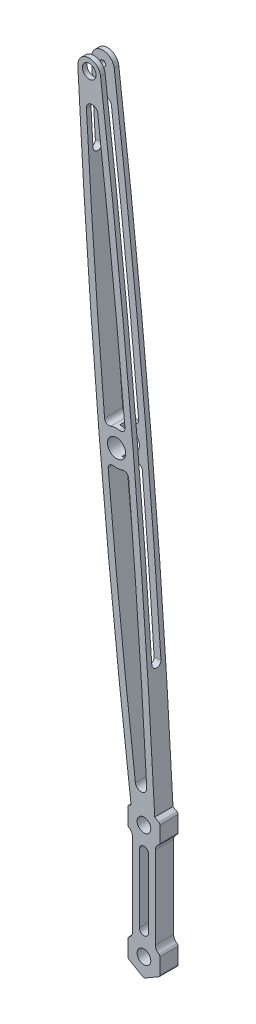
SolidWorks part; units mm, degrees
material "A2017"
ref_plane "正面" through (0, 0, 0) normal (0, 0, 1) x (1, 0, 0)
ref_plane "平面" through (0, 0, 0) normal (0, 1, 0) x (1, 0, 0)
ref_plane "右側面" through (0, 0, 0) normal (1, 0, 0) x (0, 0, -1)
sketch "ｽｹｯﾁ1" plane through (0, 0, 0) normal (0, 0, 1) x (1, 0, 0)
  line L0 (0, 0) -> (9.0749, 0) construction
  line L1 (0, 25) -> (0, 0) construction
  line L2 (0, -16.9171) -> (7, -20.9585)
  line L3 (7, 20.9585) -> (7, 29.0415)
  line L4 (7, 29.0415) -> (0, 33.0829)
  line L5 (0, 33.0829) -> (-7, 29.0415)
  line L6 (-7, 29.0415) -> (-7, 20.9585)
  line L7 (-7, 20.9585) -> (0, 16.9171)
  line L8 (0, 16.9171) -> (7, 20.9585)
  line L9 (-7, -20.9585) -> (0, -16.9171)
  line L10 (-7, -29.0415) -> (-7, -20.9585)
  line L11 (0, -33.0829) -> (-7, -29.0415)
  line L12 (7, -29.0415) -> (0, -33.0829)
  line L13 (7, -20.9585) -> (7, -29.0415)
  circle A0 centre (0, 25) radius 3
  circle A1 centre (0, -25) radius 3
  circle A2 centre (0, 25) radius 7 construction
  circle A3 centre (0, -25) radius 7 construction
  dimension "D1" = 6
  dimension "D2" = 50
  dimension "D3" = 14
extrude "ﾎﾞｽ - 押し出し1" add sketch "ｽｹｯﾁ1" along normal mid plane 8
sketch "ｽｹｯﾁ2" plane through (0, 0, 4) normal (0, 0, 1) x (1, 0, 0)
  line L0 (-7, 20.9585) -> (0, 16.9171) construction
  line L1 (5, -19.8038) -> (-5, -19.8038)
  line L2 (5, -19.8038) -> (5, 19.8038)
  line L3 (5, 19.8038) -> (-5, 19.8038)
  line L4 (-5, -19.8038) -> (-5, 19.8038)
  line L5 (5, -19.8038) -> (-5, 19.8038) construction
  line L6 (5, 19.8038) -> (-5, -19.8038) construction
  point P0 (0, 0)
  dimension "D1" = 10
extrude "ﾎﾞｽ - 押し出し2" add sketch "ｽｹｯﾁ2" against normal up to surface (8 mm away) up to face at (0, 25, -4)
fillet "ﾌｨﾚｯﾄ1" radius 3 4 edges at (5, -19.8038, 0) (-5, 19.8038, 0) (-5, -19.8038, 0) (5, 19.8038, 0)
fillet "ﾌｨﾚｯﾄ2" radius 1 10 edges at (-7, 20.9585, 0) (-7, 29.0415, 0) (0, 33.0829, 0) (7, 29.0415, 0) (7, 20.9585, 0) (7, -29.0415, 0) (0, -33.0829, 0) (-7, -29.0415, 0) (-7, -20.9585, 0) (7, -20.9585, 0)
sketch "ｽｹｯﾁ3" plane through (0, 0, -4) normal (0, 0, -1) x (-1, 0, 0)
  line L0 (0, -15) -> (0, 15) construction
  line L1 (-2, -15) -> (-2, 15)
  line L2 (2, -15) -> (2, 15)
  arc A0 (-2, -15) -> (2, -15) centre (0, -15) ccw
  arc A1 (2, 15) -> (-2, 15) centre (0, 15) ccw
  point P2 (0, 0)
  dimension "D1" = 4
  dimension "D2" = 30
extrude "ｶｯﾄ - 押し出し1" cut sketch "ｽｹｯﾁ3" against normal up to surface (8 mm away) up to face at (0, 0, 4)
sketch "ｽｹｯﾁ5" plane through (0, 0, 4) normal (0, 0, 1) x (1, 0, 0)
  circle A0 centre (0, -25) radius 3 construction
  circle A1 centre (0, 25) radius 3 construction
  circle A2 centre (0, -25) radius 3
  circle A3 centre (0, 25) radius 3
extrude "ﾎﾞｽ - 押し出し3" [suppressed] add sketch "ｽｹｯﾁ5" against normal blind 5
sketch "ｽｹｯﾁ8" plane through (0, 0, -4) normal (0, 0, -1) x (-1, 0, 0)
  circle A0 centre (0, -25) radius 3 construction
  circle A1 centre (0, 25) radius 3 construction
  circle A2 centre (0, -25) radius 3
  circle A3 centre (0, 25) radius 3
extrude "ﾎﾞｽ - 押し出し4" add sketch "ｽｹｯﾁ8" against normal blind 2.5
hole_wizard "M3 すきま穴1" positions "ｽｹｯﾁ6" profile "ｽｹｯﾁ7" hole size "M3" standard "JIS" end condition through all
sketch "ｽｹｯﾁ6" plane through (0, 0, 4) normal (0, 0, -1) x (-1, 0, 0)
  point P0 (0, 25)
  point P3 (0, -25)
sketch "ｽｹｯﾁ7" plane through (0, 25, 4) normal (1, 0, 0) x (0, -1, 0)
  line L0 (0, 0) -> (0, 8)
  line L1 (0, 8) -> (1.7, 8)
  line L2 (1.7, 8) -> (1.7, 0)
  line L5 (1.7, 0) -> (0, 0)
  line L11 (0, -6.35) -> (0, 107.95) construction
  dimension "通し穴の直径" = 3.4
  dimension "通し穴の深さ" = 8
sketch "ｽｹｯﾁ9" plane through (0, 0, 4) normal (0, 0, 1) x (1, 0, 0)
  line L0 (0, 25) -> (0, 298.9535) construction
  line L1 (0, 25) -> (-23.9678, 298.9535) construction
  line L2 (0, 25) -> (-23.9678, 298.9535) construction
  line L3 (-7.4715, 24.3463) -> (-31.4393, 298.2999) construction
  line L4 (7.4715, 25.6537) -> (-16.4964, 299.6072) construction
  line L15 (-7, 28.4641) -> (-7, 21.5359)
  line L16 (-5, 18.0718) -> (-5, -18.0718)
  line L17 (-7, -21.5359) -> (-7, -28.4641)
  line L18 (-6.5, -29.3301) -> (-0.5, -32.7942)
  line L19 (0.5, -32.7942) -> (6.5, -29.3301)
  line L20 (7, -28.4641) -> (7, -21.5359)
  line L21 (5, -18.0718) -> (5, 18.0718)
  line L22 (7, 21.5359) -> (7, 28.4641)
  line L23 (6.5, 29.3301) -> (0.5, 32.7942)
  line L24 (-0.5, 32.7942) -> (-6.5, 29.3301)
  line L25 (-7, 28.4641) -> (-7, 21.5359)
  line L26 (-5, 18.0718) -> (-5, -18.0718)
  line L27 (-7, -21.5359) -> (-7, -28.4641)
  line L28 (-6.5, -29.3301) -> (-0.5, -32.7942)
  line L29 (0.5, -32.7942) -> (6.5, -29.3301)
  line L30 (7, -28.4641) -> (7, -21.5359)
  line L31 (5, -18.0718) -> (5, 18.0718)
  line L32 (7, 21.5359) -> (7, 28.4641)
  line L33 (6.5, 29.3301) -> (0.5, 32.7942)
  line L34 (-0.5, 32.7942) -> (-6.5, 29.3301)
  arc A0 (-7.4715, 24.3463) -> (7.4715, 25.6537) centre (0, 25) ccw construction
  arc A1 (-16.4964, 299.6072) -> (-31.4393, 298.2999) centre (-23.9678, 298.9535) ccw construction
  circle A2 centre (-23.9678, 298.9535) radius 5 construction
  circle A3 centre (0, 25) radius 5
  arc A4 (-19.006, 299.5701) -> (4.9935, 25.2544) centre (-3777.5999, -167.4719) cw
  arc A5 (-28.9614, 298.6991) -> (-4.9618, 24.3834) centre (3753.632, 491.4255) ccw
  arc A6 (-19.006, 299.5701) -> (-28.9614, 298.6991) centre (-23.9678, 298.9535) ccw
  arc A16 (-7, 21.5359) -> (-6.5, 20.6699) centre (-6, 21.5359) ccw
  arc A17 (-5, 18.0718) -> (-6.5, 20.6699) centre (-8, 18.0718) ccw
  arc A18 (-6.5, -20.6699) -> (-5, -18.0718) centre (-8, -18.0718) ccw
  arc A19 (-6.5, -20.6699) -> (-7, -21.5359) centre (-6, -21.5359) ccw
  arc A20 (-7, -28.4641) -> (-6.5, -29.3301) centre (-6, -28.4641) ccw
  arc A21 (-0.5, -32.7942) -> (0.5, -32.7942) centre (0, -31.9282) ccw
  arc A22 (6.5, -29.3301) -> (7, -28.4641) centre (6, -28.4641) ccw
  arc A23 (7, -21.5359) -> (6.5, -20.6699) centre (6, -21.5359) ccw
  arc A24 (5, -18.0718) -> (6.5, -20.6699) centre (8, -18.0718) ccw
  arc A25 (6.5, 20.6699) -> (5, 18.0718) centre (8, 18.0718) ccw
  arc A26 (6.5, 20.6699) -> (7, 21.5359) centre (6, 21.5359) ccw
  arc A27 (7, 28.4641) -> (6.5, 29.3301) centre (6, 28.4641) ccw
  arc A28 (0.5, 32.7942) -> (-0.5, 32.7942) centre (0, 31.9282) ccw
  arc A29 (-6.5, 29.3301) -> (-7, 28.4641) centre (-6, 28.4641) ccw
  arc A30 (-7, 21.5359) -> (-6.5, 20.6699) centre (-6, 21.5359) ccw
  arc A31 (-5, 18.0718) -> (-6.5, 20.6699) centre (-8, 18.0718) ccw
  arc A32 (-6.5, -20.6699) -> (-5, -18.0718) centre (-8, -18.0718) ccw
  arc A33 (-6.5, -20.6699) -> (-7, -21.5359) centre (-6, -21.5359) ccw
  arc A34 (-7, -28.4641) -> (-6.5, -29.3301) centre (-6, -28.4641) ccw
  arc A35 (-0.5, -32.7942) -> (0.5, -32.7942) centre (0, -31.9282) ccw
  arc A36 (6.5, -29.3301) -> (7, -28.4641) centre (6, -28.4641) ccw
  arc A37 (7, -21.5359) -> (6.5, -20.6699) centre (6, -21.5359) ccw
  arc A38 (5, -18.0718) -> (6.5, -20.6699) centre (8, -18.0718) ccw
  arc A39 (6.5, 20.6699) -> (5, 18.0718) centre (8, 18.0718) ccw
  arc A40 (6.5, 20.6699) -> (7, 21.5359) centre (6, 21.5359) ccw
  arc A41 (7, 28.4641) -> (6.5, 29.3301) centre (6, 28.4641) ccw
  arc A42 (0.5, 32.7942) -> (-0.5, 32.7942) centre (0, 31.9282) ccw
  arc A43 (-6.5, 29.3301) -> (-7, 28.4641) centre (-6, 28.4641) ccw
  point P4 (-11.9839, 161.9768)
  dimension "D5" = 10
  dimension "D1" = 5
  dimension "D2" = 275
  dimension "D4" = 15
  dimension "D3" = 0
extrude "ﾎﾞｽ - 押し出し5" add sketch "ｽｹｯﾁ9" against normal up to surface (8 mm away) contours A4 A6 A5 L33 region at (-12.3318, 165.9529, 4) up to face at (1.7, 25, -4)
sketch "ｽｹｯﾁ12" plane through (0, 0, -4) normal (0, 0, -1) x (-1, 0, 0)
  line L0 (23.9678, 298.9535) -> (0, 25) construction
hole_wizard "M3 ねじ穴1" positions "ｽｹｯﾁ19" profile "ｽｹｯﾁ20" tap size "M3" standard "JIS" end condition through all
sketch "ｽｹｯﾁ19" plane through (0, 0, 4) normal (0, 0, 1) x (1, 0, 0)
  point P0 (-23.9678, 298.9535)
sketch "ｽｹｯﾁ20" plane through (-23.9678, 298.9535, 4) normal (1, 0, 0) x (0, -1, 0)
  line L0 (0, 0) -> (0, 8)
  line L1 (0, 8) -> (1.25, 8)
  line L2 (1.25, 8) -> (1.25, 0)
  line L5 (1.25, 0) -> (0, 0)
  line L11 (0, -6.35) -> (0, 107.95) construction
  dimension "次ｻｰﾌｪｽまでのねじ下穴ﾄﾞﾘﾙ直径" = 2.5
  dimension "次ｻｰﾌｪｽまでのねじ下穴ﾄﾞﾘﾙの深さ" = 8
cosmetic thread "穴のねじ山1" parameters "D2"=3
sketch "ｽｹｯﾁ10" plane through (0, 0, 4) normal (0, 0, 1) x (1, 0, 0)
  circle A0 centre (-23.9678, 298.9535) radius 3
  dimension "D1" = 6
extrude "ｶｯﾄ - 押し出し2" cut sketch "ｽｹｯﾁ10" against normal blind 6
sketch "ｽｹｯﾁ21" plane through (0, 0, -4) normal (0, 0, -1) x (-1, 0, 0)
  circle A0 centre (23.9678, 298.9535) radius 3
  dimension "D1" = 6
extrude "ｶｯﾄ - 押し出し8" [suppressed] cut sketch "ｽｹｯﾁ21" against normal blind 6
ref_plane "平面1" through (2.1706, 0.1899, 0) normal (0.9962, 0.0872, 0) x (0.0872, -0.9962, 0)
sketch "ｽｹｯﾁ13" plane through (0, 0, -4) normal (0, 0, -1) x (-1, 0, 0)
  line L0 (23.9678, 298.9535) -> (0, 25) construction
  arc A2 (21.9831, 299.2002) -> (-1.7345, 30.1951) centre (3777.5999, -167.4719) ccw
  arc A3 (21.9831, 299.2002) -> (-1.7345, 30.1951) centre (3777.5999, -167.4719) ccw
  arc A4 (25.1986, 284.3517) -> (20.2202, 284.7872) centre (22.7023, 284.4885) ccw
  arc A5 (2.657, 30.1954) -> (25.9652, 298.8518) centre (-3753.632, 491.4255) ccw
  arc A6 (2.657, 30.1954) -> (25.9652, 298.8518) centre (-3753.632, 491.4255) ccw
  arc A7 (-1.2307, 39.6019) -> (3.7476, 39.1663) centre (1.2655, 39.4651) ccw
  dimension "D3" = 5
  dimension "D1" = 3
  dimension "D2" = 3
extrude "ｶｯﾄ - 押し出し3" cut sketch "ｽｹｯﾁ13" against normal through all contours A3 A7 A6 A4 region at (-11.9839, 161.9768, -4)
sketch "ｽｹｯﾁ14" plane through (0, 0, -4) normal (0, 0, -1) x (-1, 0, 0)
  line L0 (16.4668, 161.5846) -> (7.501, 162.369) construction
  arc A0 (3.7476, 39.1663) -> (25.1986, 284.3517) centre (-3753.632, 491.4255) ccw construction
  arc A1 (20.2202, 284.7872) -> (-1.2307, 39.6019) centre (3777.5999, -167.4719) ccw construction
  circle A2 centre (11.9839, 161.9768) radius 7.5
  arc A3 (5.6346, 29.8298) -> (28.9614, 298.6991) centre (-3753.632, 491.4255) ccw construction
extrude "ﾎﾞｽ - 押し出し6" add sketch "ｽｹｯﾁ14" against normal up to surface (8 mm away) up to face at (-11.9839, 161.9768, 4)
fillet "ﾌｨﾚｯﾄ3" radius 2 4 edges at (-6.9825, 156.3878, 0) (-15.9388, 155.6043, 0) (-16.9853, 167.5657, 0) (-8.029, 168.3493, 0)
sketch "ｽｹｯﾁ15" plane through (0, 0, 4) normal (0, 0, 1) x (1, 0, 0)
  line L0 (-23.9678, 298.9535) -> (0, 25) construction
  circle A0 centre (-11.9839, 161.9768) radius 4
  dimension "D1" = 8
extrude "ｶｯﾄ - 押し出し4" cut sketch "ｽｹｯﾁ15" against normal through all
sketch "ｽｹｯﾁ16" plane through (2.1706, 0.1899, 0) normal (0.9962, 0.0872, 0) x (0.0872, -0.9962, 0)
  line L0 (-304.9049, 0) -> (-84.9049, 0) construction
  line L1 (-304.9049, 4) -> (-304.9049, -4) construction
  line L2 (-304.9049, 2) -> (-84.9049, 2)
  line L3 (-304.9049, -2) -> (-84.9049, -2)
  arc A0 (-304.9049, 2) -> (-304.9049, -2) centre (-304.9049, 0) ccw
  arc A1 (-84.9049, -2) -> (-84.9049, 2) centre (-84.9049, 0) ccw
  point P5 (-194.9049, 0)
  dimension "D1" = 4
  dimension "D2" = 220
extrude "ｶｯﾄ - 押し出し6" cut sketch "ｽｹｯﾁ16" along normal through all
sketch "ｽｹｯﾁ22" plane through (2.1706, 0.1899, 0) normal (0.9962, 0.0872, 0) x (0, 0, -1)
  line L0 (0, 304.9049) -> (0, 269.9049) construction
  line L1 (-2, 304.9049) -> (2, 304.9049) construction
  line L2 (2, 304.9049) -> (2, 269.9049)
  line L3 (-2, 304.9049) -> (-2, 269.9049)
  line L4 (2, 302.9049) -> (2, 304.9049) construction
  arc A0 (2, 304.9049) -> (-2, 304.9049) centre (0, 304.9049) ccw
  arc A1 (-2, 269.9049) -> (2, 269.9049) centre (0, 269.9049) ccw
  point P5 (0, 287.4049)
  dimension "D1" = 35
extrude "ｶｯﾄ - 押し出し9" cut sketch "ｽｹｯﾁ22" against normal through all
